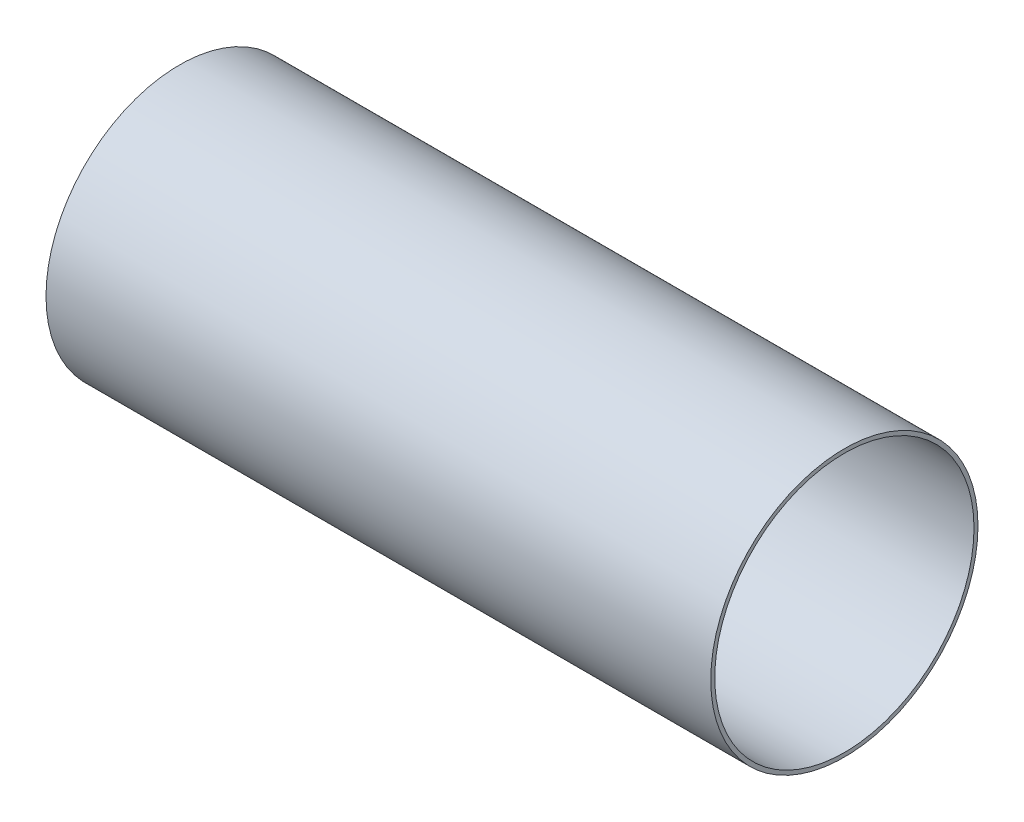
SolidWorks part; units mm, degrees
ref_plane "Front Plane" through (0, 0, 0) normal (1, 0, 0) x (0, 1, 0)
ref_plane "Top Plane" through (0, 0, 0) normal (0, 0, 1) x (0, 1, 0)
ref_plane "Right Plane" through (0, 0, 0) normal (0, 1, 0) x (-1, 0, 0)
sketch "Sketch1" plane through (0, 0, 0) normal (1, 0, 0) x (0, 1, 0)
  circle A0 centre (0, 0) radius 51.054
  circle A1 centre (0, 0) radius 49.53
  dimension "D1" = 102.108
  dimension "D2" = 99.06
extrude "Boss-Extrude1" add sketch "Sketch1" along normal blind 127 and the other way blind 127
